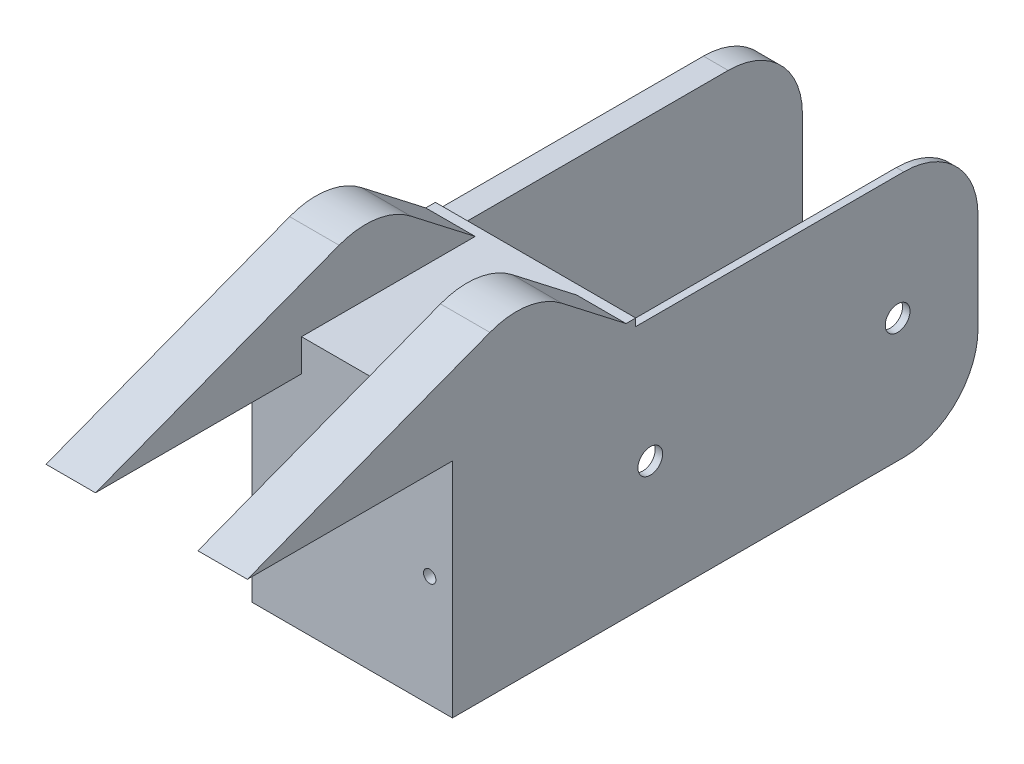
SolidWorks part; units mm, degrees
ref_plane "前视基准面" through (0, 0, 0) normal (0, 0, 1) x (1, 0, 0)
ref_plane "上视基准面" through (0, 0, 0) normal (0, 1, 0) x (1, 0, 0)
ref_plane "右视基准面" through (0, 0, 0) normal (1, 0, 0) x (0, 0, -1)
other "Configuration Table"
sketch "草图1" plane through (0, 0, 0) normal (0, 1, 0) x (1, 0, 0)
  line L0 (50, 0) -> (50, 85.1816) construction
  line L1 (0, 0) -> (100, 0)
  line L2 (0, 0) -> (0, -100)
  line L3 (0, -100) -> (100, -100)
  line L4 (100, 0) -> (100, -100)
  line L5 (9.5, 75.0478) -> (9.5, 17.1128) construction
  line L6 (90.5, 75.0478) -> (90.5, 17.1128) construction
  line L7 (-7.6482, 80) -> (134.4168, 80) construction
  line L8 (0, 0) -> (9.5, 12.5)
  line L9 (100, 0) -> (90.5, 12.5)
  line L10 (90.5, 12.5) -> (90.5, 212.5)
  line L11 (90.5, 212.5) -> (9.5, 212.5)
  line L12 (9.5, 212.5) -> (9.5, 12.5)
  line L13 (90.5, 12.5) -> (90.5, 0)
  line L14 (9.5, 12.5) -> (9.5, 0)
  dimension "D1" = 100
  dimension "D2" = 100
  dimension "D3" = 81
  dimension "D4" = 80
  dimension "D5" = 200
extrude "凸台-拉伸1" add sketch "草图1" along normal blind 50 and the other way blind 50 contours L12 L14 L1 L13 L10 L11 region at (50, 0, -106.25)
ref_plane "基准面1" through (0, 0, 0) normal (0, -1, 0) x (-1, 0, 0)
sketch "草图2" plane through (0, 0, 0) normal (0, -1, 0) x (-1, 0, 0)
  line L0 (-130.3132, 0) -> (40.2206, 0) construction
  line L1 (-150, 0) -> (-150, -100)
  line L2 (-150, -100) -> (50, -100)
  line L3 (50, -100) -> (50, 0)
  line L4 (50, 0) -> (-150, 0)
  line L5 (-50, 212.5) -> (-50, 195.989) construction
  line L6 (-90.5, 212.5) -> (-9.5, 212.5) construction
  point P10 (-50, 212.5)
  dimension "D1" = 200
  dimension "D2" = 100
extrude "凸台-拉伸2" add sketch "草图2" against normal blind 40
ref_plane "基准面2" through (0, 0, 100) normal (0, 0, 1) x (1, 0, 0)
sketch "草图3" plane through (0, 0, 100) normal (0, 0, 1) x (1, 0, 0)
  line L0 (-50, 37) -> (150, 37)
  line L1 (-50, 40) -> (-50, 0) construction
  line L2 (150, 40) -> (150, 0) construction
  line L3 (150, 37) -> (150, 3)
  line L4 (150, 3) -> (-50, 3)
  line L5 (-50, 3) -> (-50, 37)
  line L6 (150, 0) -> (-50, 0) construction
  line L7 (150, 40) -> (-50, 40) construction
  dimension "D1" = 3
  dimension "D2" = 3
extrude "切除-拉伸1" cut sketch "草图3" against normal blind 100
ref_plane "基准面3" through (34.5, 0, 0) normal (-1, 0, 0) x (0, 0, 1)
ref_plane "基准面4" through (0, 50, 0) normal (0, 1, 0) x (1, 0, 0)
sketch "草图6" plane through (0, 50, 0) normal (0, 1, 0) x (1, 0, 0)
  line L0 (12.5, 212.5) -> (12.5, 5)
  line L1 (90.5, 212.5) -> (9.5, 212.5) construction
  line L2 (12.5, 5) -> (87.5, 5)
  line L3 (87.5, 5) -> (87.5, 212.5)
  line L4 (9.5, 212.5) -> (9.5, 0) construction
  line L5 (90.5, 212.5) -> (90.5, 0) construction
  line L7 (9.5, 0) -> (90.5, 0) construction
  dimension "D1" = 3
  dimension "D2" = 3
  dimension "D3" = 5
extrude "切除-拉伸2" cut sketch "草图6" against normal through all
ref_plane "基准面5" through (0, 40, 0) normal (0, 1, 0) x (1, 0, 0)
sketch "草图8" plane through (0, 40, 0) normal (0, 1, 0) x (1, 0, 0)
  line L0 (-50, -50) -> (102.2011, -50) construction
  line L1 (-50, -100) -> (-50, 0) construction
  line L2 (50, 0) -> (50, -100) construction
  line L3 (9.5, 0) -> (90.5, 0) construction
  line L4 (-22, -100) -> (22, -100) construction
  circle A0 centre (70, -50) radius 2.5
  circle A1 centre (30, -50) radius 2.5
  dimension "D1" = 5
  dimension "D2" = 5
  dimension "D3" = 40
extrude "切除-拉伸4" cut sketch "草图8" against normal through all
ref_plane "基准面6" through (90.5, 0, 0) normal (1, 0, 0) x (0, 0, -1)
sketch "草图10" plane through (90.5, 0, 0) normal (1, 0, 0) x (0, 0, -1)
  line L0 (39.5916, 0) -> (155.7144, 0) construction
  line L2 (0, 37) -> (0, 3) construction
  circle A0 centre (80, 0) radius 5
  circle A1 centre (180, 0) radius 5
  dimension "D3" = 10
  dimension "D4" = 10
  dimension "D1" = 80
  dimension "D2" = 180
extrude "切除-拉伸5" cut sketch "草图10" against normal through all
sketch "草图11" plane through (9.5, 0, 0) normal (-1, 0, 0) x (0, 0, 1)
  line L2 (-30.9056, 83.4152) -> (-74.0944, 50)
  line L3 (44.55, 50) -> (-44.55, 50) construction
  line L4 (-74.0944, 50) -> (0, 50)
  line L5 (0, 40) -> (0, 50) construction
  line L6 (0, 50) -> (0, 40)
  line L8 (-30.9056, 83.4152) -> (83.321, 40)
  line L9 (100, 40) -> (0, 40) construction
  line L10 (83.321, 40) -> (0, 40)
extrude "凸台-拉伸5" add sketch "草图11" against normal blind 20
sketch "草图13" plane through (90.5, 0, 0) normal (1, 0, 0) x (0, 0, -1)
  line L0 (0, 36.2107) -> (0, 62.8442) construction
  line L1 (44.55, 50) -> (-44.55, 50) construction
  line L2 (74.1158, 50) -> (0, 50)
  line L3 (74.1158, 50) -> (74.1158, 53)
  line L4 (74.1158, 53) -> (0, 53)
  line L5 (0, 50) -> (0, 53)
  dimension "D1" = 3
extrude "凸台-拉伸7" add sketch "草图13" against normal blind 81
ref_plane "基准面7" through (12.5, 0, 0) normal (1, 0, 0) x (0, 0, -1)
sketch "草图14" plane through (12.5, 0, 0) normal (1, 0, 0) x (0, 0, -1)
  line L0 (5, -46.5508) -> (5, 34.4221) construction
  line L2 (5, -50) -> (212.5, -50)
  line L3 (212.5, -50) -> (212.5, 50)
  line L4 (44.55, 50) -> (-44.55, 50) construction
  line L5 (212.5, -50) -> (212.5, 50) construction
  line L6 (212.5, 50) -> (5, 50)
  line L7 (5, 50) -> (5, -50)
extrude "凸台-拉伸8" add sketch "草图14" along normal blind 7
sketch "草图15" plane through (90.5, 0, 0) normal (1, 0, 0) x (0, 0, -1)
  line L0 (30.9056, 83.4152) -> (-82.9022, 40)
  line L1 (55, 40) -> (-55, 40) construction
  line L2 (-82.9022, 40) -> (0, 40)
  line L3 (0, 37) -> (0, 40) construction
  line L4 (0, 40) -> (0, 53)
  line L5 (0, 53) -> (70.217, 53)
  line L6 (70.217, 53) -> (30.9056, 83.4152)
extrude "凸台-拉伸9" add sketch "草图15" against normal blind 20
ref_plane "基准面8" through (0, 37, 0) normal (0, -1, 0) x (-1, 0, 0)
ref_plane "基准面9" through (0, 3, 0) normal (0, 1, 0) x (1, 0, 0)
sketch "草图17" plane through (0, 37, 0) normal (0, -1, 0) x (-1, 0, 0)
  circle A0 centre (-30, -50) radius 6.35
  dimension "D1" = 12.7
extrude "切除-拉伸6" cut sketch "草图17" against normal blind 1
sketch "草图18" plane through (0, 3, 0) normal (0, 1, 0) x (1, 0, 0)
  circle A0 centre (30, -50) radius 6.35
  dimension "D1" = 12.7
extrude "切除-拉伸7" cut sketch "草图18" against normal blind 1
sketch "草图20" plane through (0, 0, 0) normal (0, -1, 0) x (1, 0, 0)
  line L0 (7.57, 50) -> (34.6356, 50) construction
  line L1 (30, 52.5) -> (30, 68.4286) construction
  circle A1 centre (-31.25, 50) radius 5
  circle A2 centre (91.25, 50) radius 5
  dimension "D2" = 10
  dimension "D4" = 10
  dimension "D1" = 61.25
  dimension "D3" = 61.25
extrude "切除-拉伸8" cut sketch "草图20" against normal blind 3
cosmetic thread "装饰螺纹线1" parameters "D2"=11
cosmetic thread "装饰螺纹线2" parameters "D2"=11
sketch "草图21" plane through (0, 3, 0) normal (0, 1, 0) x (1, 0, 0)
  line L0 (118.3346, -100) -> (118.3346, 0)
  line L1 (-1.65, -100) -> (1.65, -100) construction
  line L2 (90.5, 0) -> (150, 0) construction
  line L3 (118.3346, 0) -> (150, 0)
  line L4 (150, 0) -> (150, -100)
  line L5 (150, 0) -> (150, -100) construction
  line L6 (150, -100) -> (118.3346, -100)
extrude "切除-拉伸9" cut sketch "草图21" along normal through all both and the other way through all
sketch "草图22" plane through (0, 0, 0) normal (0, -1, 0) x (1, 0, 0)
  line L0 (-38.0419, 14.9384) -> (110.8032, 14.9384) construction
  circle A0 centre (-28.835, 14.9384) radius 5
  circle A1 centre (99.9437, 14.9384) radius 5
  circle A2 centre (47.3586, 88.9028) radius 5
  dimension "D1" = 10
  dimension "D2" = 10
  dimension "D3" = 10
extrude "凸台-拉伸10" add sketch "草图22" against normal up to surface (37 mm away) up to face at (70, 37, 52.5)
fillet "圆角1" radius 30 10 edges at (19.5, 83.4152, -30.9056) (80.5, 83.4152, -30.9056) (118.3346, 38.5, 0) (118.3346, 1.5, 0) (118.3346, 38.5, 100) (118.3346, 1.5, 100) (-50, 38.5, 100) (-50, 38.5, 0) (-50, 1.5, 0) (-50, 1.5, 100)
fillet "圆角2" radius 30 4 edges at (89, -50, -212.5) (89, 50, -212.5) (14.5, 50, -212.5) (14.5, -50, -212.5)
sketch "草图23" plane through (90.5, 0, 0) normal (1, 0, 0) x (0, 0, -1)
  line L0 (55, 40) -> (-55, 40) construction
  line L1 (0, 40) -> (-125.5874, 40)
  line L2 (0, 40) -> (0, -27.2465)
  line L3 (0, -27.2465) -> (-125.5874, -27.2465)
  line L4 (-125.5874, 40) -> (-125.5874, -27.2465)
extrude "切除-拉伸10" cut sketch "草图23" against normal through all both and the other way through all
sketch "草图24" plane through (0, 40, 0) normal (0, -1, 0) x (1, 0, 0)
  line L0 (80.5, 0) -> (80.5, 21.6945) construction
  line L1 (70.5, 0) -> (90.5, 0) construction
  line L2 (19.5, 0) -> (19.5, 24.5958) construction
  line L3 (9.5, 0) -> (29.5, 0) construction
  circle A0 centre (80.5, 8.6731) radius 5
  circle A1 centre (19.5, 8.6731) radius 5
  dimension "D1" = 10
  dimension "D2" = 10
extrude "切除-拉伸11" cut sketch "草图24" against normal blind 5
cosmetic thread "装饰螺纹线5" parameters "D2"=11
cosmetic thread "装饰螺纹线6" parameters "D2"=11
sketch "草图25" plane through (0, 0, 0) normal (0, 0, 1) x (1, 0, 0)
  line L0 (80.5, 0) -> (110.5, 0) construction
  circle A0 centre (81.3169, -5) radius 2.5
  dimension "D1" = 5
  dimension "D2" = 5
extrude "切除-拉伸12" cut sketch "草图25" against normal blind 50
cosmetic thread "装饰螺纹线7" parameters "D2"=6
